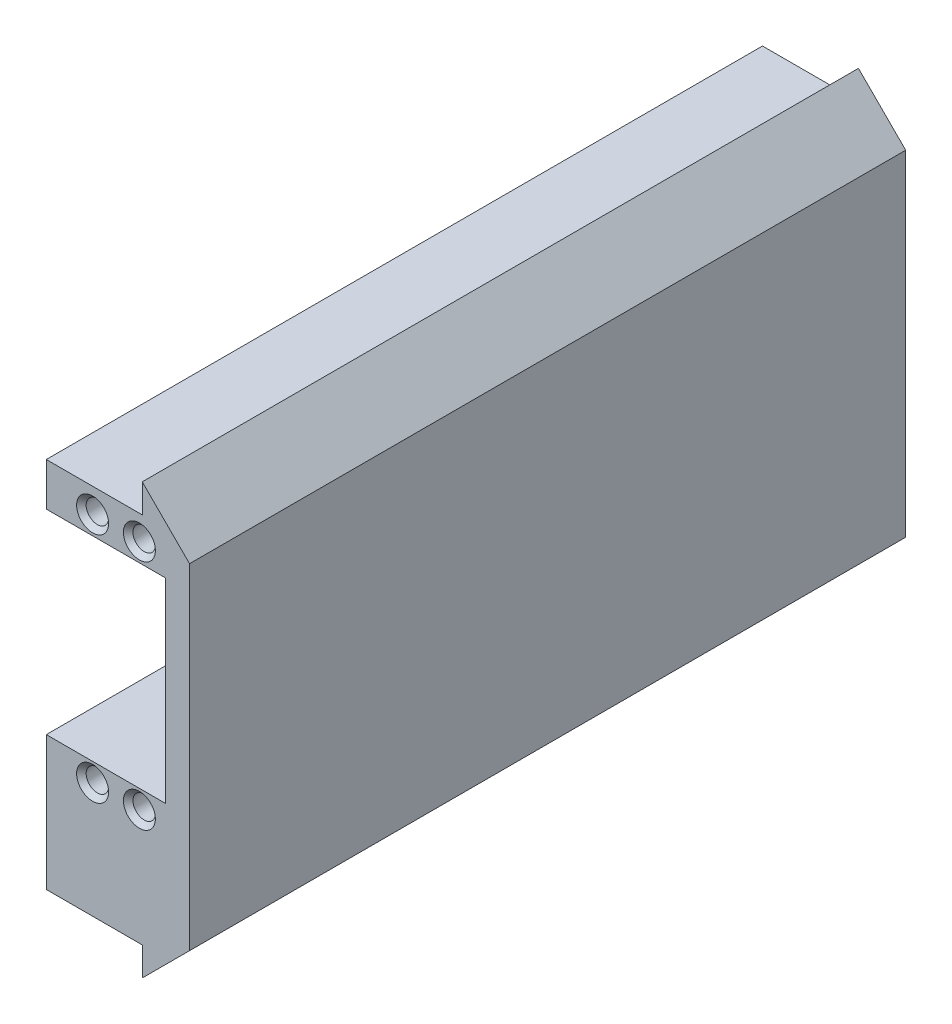
SolidWorks part; units mm, degrees
material "ABS"
ref_plane "Front Plane" through (0, 0, 0) normal (0, 0, 1) x (1, 0, 0)
ref_plane "Top Plane" through (0, 0, 0) normal (0, 1, 0) x (1, 0, 0)
ref_plane "Right Plane" through (0, 0, 0) normal (1, 0, 0) x (0, 0, -1)
sketch "Sketch1" plane through (0, 0, 0) normal (0, 0, 1) x (1, 0, 0)
  line L0 (-15, 45) -> (15, 45)
  line L1 (-15, 45) -> (15, 45) construction
  line L2 (-15, 45) -> (-15, -45) construction
  line L3 (-15, -45) -> (15, -45) construction
  line L4 (15, 45) -> (15, -45) construction
  line L5 (-15, 45) -> (15, -45) construction
  line L6 (-15, -45) -> (15, 45) construction
  line L7 (15, 45) -> (15, -45)
  line L8 (15, -45) -> (-15, -45)
  line L9 (-15, -45) -> (-15, -10.9)
  line L10 (-15, -10.9) -> (10, -10.9)
  line L11 (10, -10.9) -> (10, 30)
  line L12 (10, 30) -> (-15, 30)
  line L13 (-15, 30) -> (-15, 45)
  point P0 (0, 0)
  dimension "D1" = 90
  dimension "D2" = 30
  dimension "D3" = 40.9
  dimension "D4" = 15
  dimension "D5" = 5
extrude "Boss-Extrude1" add sketch "Sketch1" along normal blind 150
sketch "Sketch2" plane through (0, 0, 150) normal (0, 0, 1) x (1, 0, 0)
  line L0 (10, 30) -> (-10.8, 30) construction
  line L1 (-15, 30) -> (10, 30) construction
  line L2 (-0.4, 30) -> (-0.4, 33.89) construction
  line L3 (-0.4, 33.89) -> (4.5, 33.89) construction
  line L4 (10, 30) -> (10, -10.9) construction
  line L5 (10, 9.55) -> (15, 9.55) construction
  line L7 (15, -45) -> (15, 45) construction
  circle A0 centre (4.5, 33.89) radius 2.35
  circle A1 centre (-5.3, 33.89) radius 2.35
  circle A4 centre (4.5, -14.79) radius 2.35
  circle A5 centre (-5.3, -14.79) radius 2.35
  dimension "D4" = 4.7
  dimension "D1" = 20.8
  dimension "D2" = 3.89
  dimension "D3" = 4.9
extrude "Cut-Extrude1" cut sketch "Sketch2" against normal blind 8
sketch "Sketch3" plane through (0, 0, 0) normal (0, 0, -1) x (-1, 0, 0)
  line L0 (-10, 30) -> (10.8, 30) construction
  line L1 (15, 30) -> (-10, 30) construction
  line L2 (-10, 30) -> (-10, -10.9) construction
  line L3 (-10, 9.55) -> (-15, 9.55) construction
  line L5 (0.4, 30) -> (0.4, 33.89) construction
  line L6 (0.4, 33.89) -> (-4.5, 33.89) construction
  line L7 (-15, -45) -> (-15, 45) construction
  circle A0 centre (-4.5, 33.89) radius 2.35
  circle A1 centre (5.3, 33.89) radius 2.35
  circle A4 centre (-4.5, -14.79) radius 2.35
  circle A5 centre (5.3, -14.79) radius 2.35
  dimension "D4" = 4.7
  dimension "D1" = 20.8
  dimension "D2" = 3.89
  dimension "D3" = 4.9
extrude "Cut-Extrude2" cut sketch "Sketch3" against normal blind 8
chamfer "Chamfer1" distance 1 angle 45 8 edges at (2.15, 33.89, 0) (-2.95, 33.89, 0) (-7.65, 33.89, 150) (6.85, 33.89, 150) (2.15, -14.79, 150) (-2.95, -14.79, 150) (-7.65, -14.79, 0) (6.85, -14.79, 0)
sketch "Sketch4" plane through (0, 0, 150) normal (0, 0, 1) x (1, 0, 0)
  line L0 (0, 0) -> (15, 0) construction
  line L1 (-15, -45) -> (5.1, -45)
  line L2 (-15, -45) -> (-15, -39)
  line L3 (-15, -39) -> (5.1, -39)
  line L4 (5.1, -45) -> (5.1, -39)
  line L5 (15, -45) -> (15, 45) construction
  line L6 (-15, 39) -> (5.1, 39)
  line L7 (5.1, 45) -> (5.1, 39)
  line L8 (-15, 45) -> (5.1, 45)
  line L9 (-15, 45) -> (-15, 39)
  dimension "D1" = 6
  dimension "D2" = 20.1
extrude "Cut-Extrude3" cut sketch "Sketch4" against normal through all
chamfer "Chamfer2" distance 9.9 angle 45 2 edges at (15, -45, 75) (15, 45, 75)
